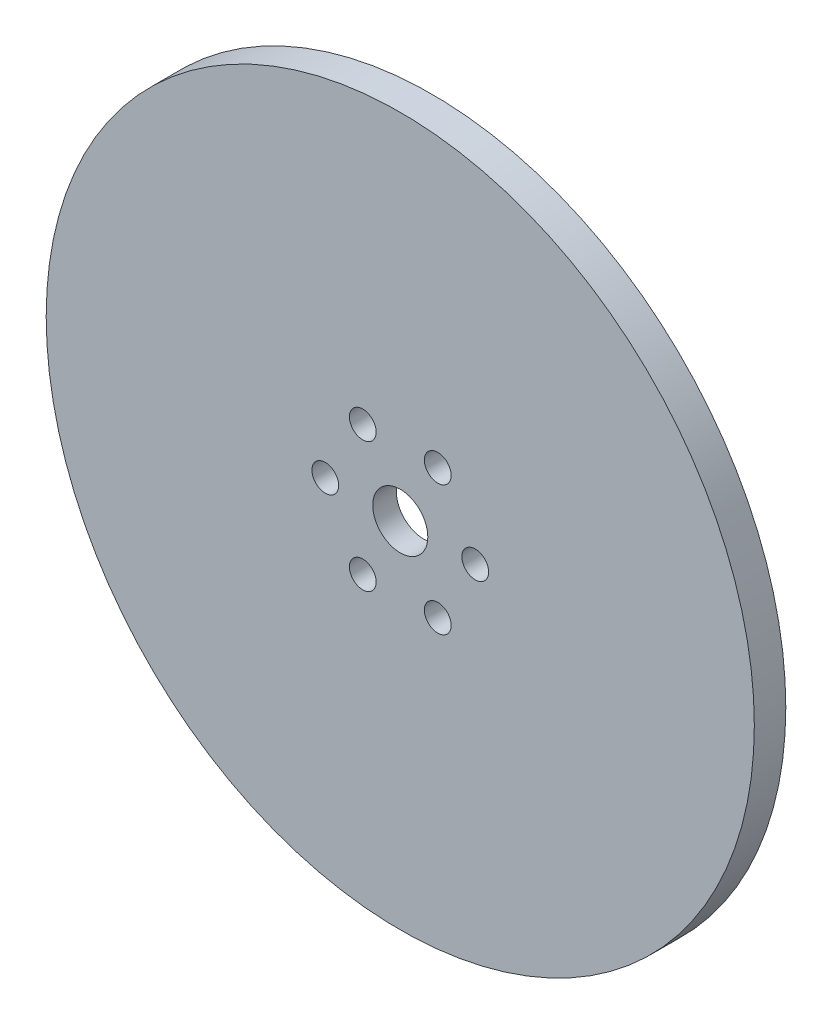
SolidWorks part; units mm, degrees
material "ABS"
ref_plane "Front Plane" through (0, 0, 0) normal (0, 0, 1) x (1, 0, 0)
ref_plane "Top Plane" through (0, 0, 0) normal (0, 1, 0) x (1, 0, 0)
ref_plane "Right Plane" through (0, 0, 0) normal (1, 0, 0) x (0, 0, -1)
sketch "Sketch1" plane through (0, 0, 0) normal (1, 0, 0) x (0, 0, -1)
  line L0 (3, 3.5) -> (6, 3.5)
  line L1 (6, 3.5) -> (6, 25)
  line L2 (6, 25) -> (7, 25)
  line L3 (7, 25) -> (7, 45)
  line L4 (7, 45) -> (3, 45)
  line L8 (0, 0) -> (3.7628, 0)
  line L9 (3, 3.5) -> (3, 45)
  dimension "D1" = 3.5
  dimension "D2" = 4
  dimension "D3" = 3
  dimension "D4" = 45
  dimension "D5" = 25
  dimension "D6" = 1
  dimension "D7" = 6
revolve "Revolve1" add sketch "Sketch1" angle 360 about L8
sketch "Sketch4" plane through (0, 0, -6) normal (0, 0, -1) x (-1, 0, 0)
  line L0 (0, 0) -> (-11.0055, 0) construction
  circle A0 centre (0, 0) radius 9.53 construction
  circle A1 centre (-9.53, 0) radius 1.7
  circle A2 centre (-4.765, 8.2532) radius 1.7
  circle A3 centre (4.765, 8.2532) radius 1.7
  circle A4 centre (9.53, 0) radius 1.7
  circle A5 centre (4.765, -8.2532) radius 1.7
  circle A6 centre (-4.765, -8.2532) radius 1.7
  point P19 (0, 0)
  dimension "D1" = 19.06
  dimension "D2" = 3.4
  dimension "D3" = 6
extrude "Cut-Extrude1" cut sketch "Sketch4" against normal blind 10
